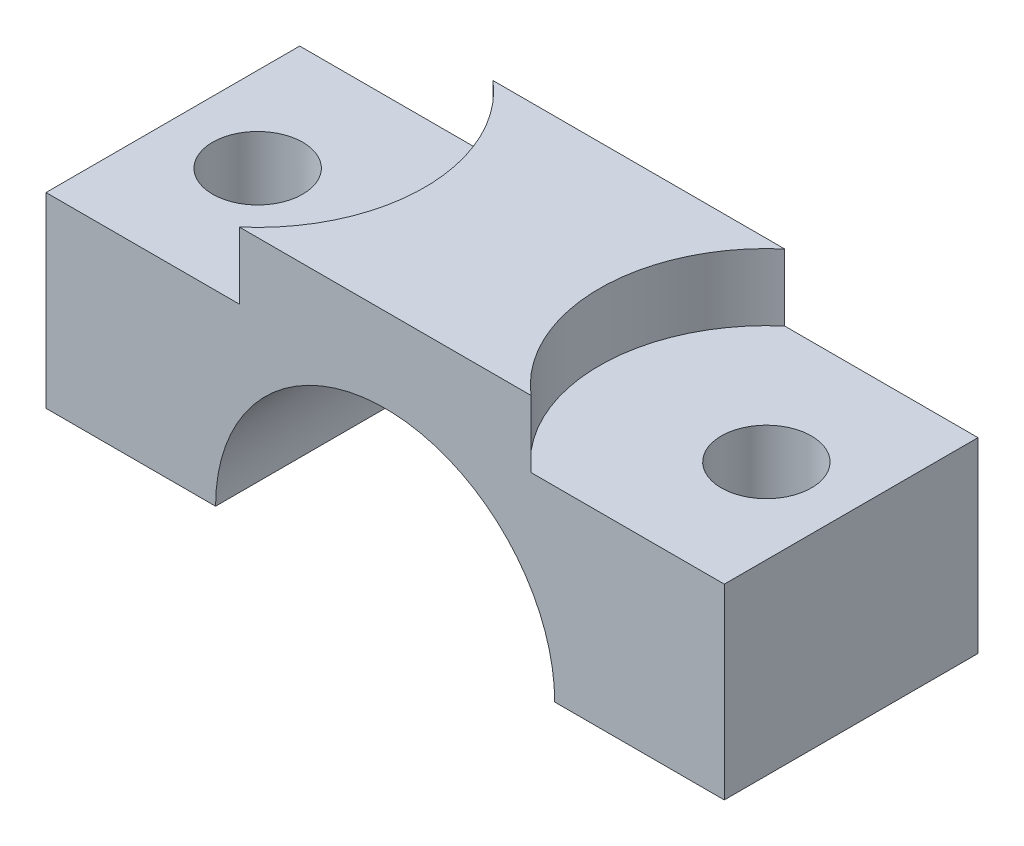
SolidWorks part; units mm, degrees
ref_plane "Front Plane" through (0, 0, 0) normal (0, 0, 1) x (1, 0, 0)
ref_plane "Top Plane" through (0, 0, 0) normal (0, 1, 0) x (1, 0, 0)
ref_plane "Right Plane" through (0, 0, 0) normal (1, 0, 0) x (0, 0, -1)
sketch "Sketch1" plane through (0, 0, 0) normal (0, 0, 1) x (1, 0, 0)
  line L0 (-12.7, 0) -> (-25.4, 0)
  line L1 (-25.4, 0) -> (-25.4, 19)
  line L2 (-25.4, 19) -> (25.4, 19)
  line L3 (0, 0) -> (0, 30.3009) construction
  line L4 (0, 19) -> (0, 12.7)
  line L5 (25.4, 0) -> (25.4, 19)
  line L6 (12.7, 0) -> (25.4, 0)
  arc A0 (-12.7, 0) -> (12.7, 0) centre (0, 0) cw
  dimension "D1" = 12.7
  dimension "D2" = 50.8
  dimension "D3" = 19
extrude "Boss-Extrude1" add sketch "Sketch1" along normal mid plane 19 contours L0 A0 L4 L2 L1 | L4 A0 L6 L5 L2 region at (-15.3017, 10.9628, 0) region at (15.3017, 10.9628, 0)
sketch "Sketch2" plane through (0, 19, 0) normal (0, 1, 0) x (1, 0, 0)
  line L0 (0, 0) -> (0, 7.3447) construction
  line L1 (-25.4, -9.5) -> (-25.4, 9.5) construction
  line L2 (-25.4, 9.5) -> (25.4, 9.5) construction
  line L3 (-25.4, -9.5) -> (25.4, -9.5) construction
  line L4 (-10.926, -9.5) -> (-25.4, -9.5)
  line L5 (-25.4, -9.5) -> (-25.4, 9.5)
  line L6 (-25.4, 9.5) -> (-10.926, 9.5)
  line L7 (25.4, -9.5) -> (25.4, 9.5)
  line L8 (10.926, -9.5) -> (25.4, -9.5)
  line L9 (25.4, 9.5) -> (10.926, 9.5)
  circle A0 centre (-19.05, 0) radius 3.375
  circle A1 centre (19.05, 0) radius 3.375
  arc A2 (-10.926, 9.5) -> (-10.926, -9.5) centre (-19.05, 0) cw
  arc A3 (10.926, 9.5) -> (10.926, -9.5) centre (19.05, 0) ccw
  line M7 (25.4, 9.5) -> (-25.4, 9.5)
  line M9 (-25.4, -9.5) -> (25.4, -9.5)
  line M10 (25.4, -9.5) -> (25.4, 9.5)
  dimension "D2" = 6.75
  dimension "D3" = 12.5
  dimension "D1" = 6.35
extrude "Cut-Extrude1" cut sketch "Sketch2" against normal blind 19 contours A1 | A0 region at (19.05, 19, 0)
extrude "Cut-Extrude2" cut sketch "Sketch2<3>" against normal blind 5 contours A3 A1 M7 M9 M10 | A2 L4 L5 L6 region at (6.8176, 19, 0)
sketch "Sketch2<3>" plane through (0, 19, 0) normal (0, 1, 0) x (1, 0, 0) same geometry as "Sketch2"
